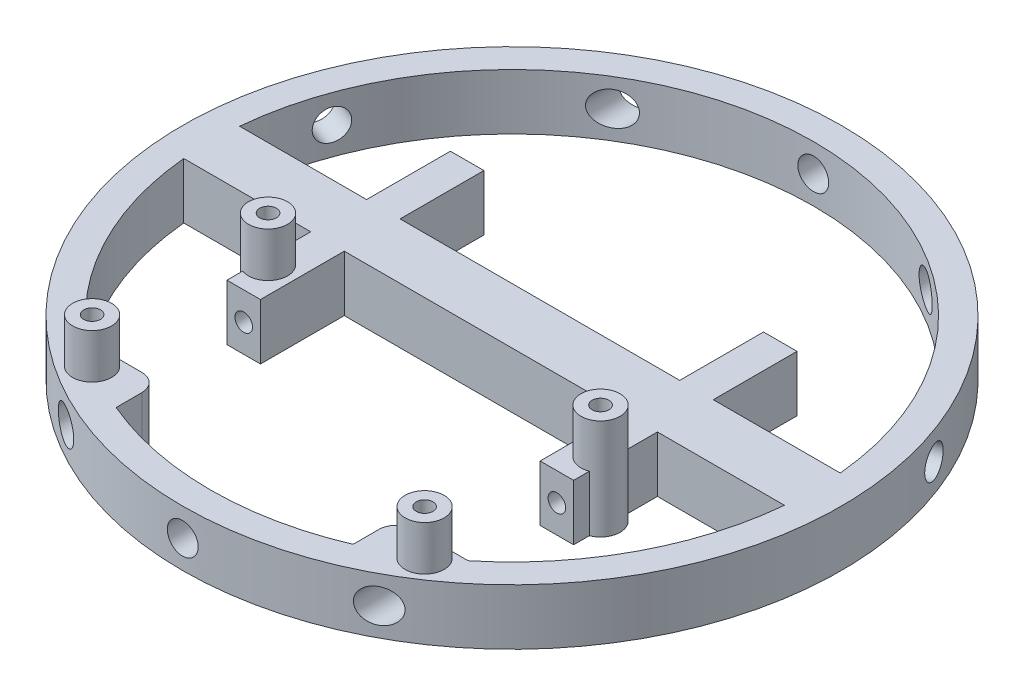
SolidWorks part; units mm, degrees
ref_plane "Front Plane" through (0, 0, 0) normal (0, 0, 1) x (1, 0, 0)
ref_plane "Top Plane" through (0, 0, 0) normal (0, 1, 0) x (1, 0, 0)
ref_plane "Right Plane" through (0, 0, 0) normal (1, 0, 0) x (0, 0, -1)
sketch "Sketch1" plane through (0, 0, 0) normal (0, 1, 0) x (1, 0, 0)
  line L5 (-50.7584, -5.9362) -> (-84.9011, -5.9362)
  line L6 (-84.9011, -5.9362) -> (-16.6157, -5.9362)
  line L9 (-84.9011, -12.2862) -> (-16.6157, -12.2862)
  circle A0 centre (-50.7584, -9.1112) radius 37.465
  circle A3 centre (-50.7584, -9.1112) radius 34.29
extrude "Boss-Extrude1" add sketch "Sketch1" along normal blind 6.35
sketch "Sketch2" plane through (0, 0, 17.0862) normal (0, 0, 1) x (1, 0, 0)
  circle A4 centre (-32.9584, 3.175) radius 0.9
  circle A5 centre (-68.5584, 3.175) radius 1
extrude "Cut-Extrude1" cut sketch "Sketch2" against normal blind 23.35
sketch "Sketch4" plane through (0, 6.35, 0) normal (0, 1, 0) x (1, 0, 0)
  line L1 (-73.4626, -34.8079) -> (-28.0542, -34.8079)
  line L5 (-69.2578, -37.9829) -> (-32.259, -37.9829)
  arc A0 (-84.9419, -11.8112) -> (-16.5749, -11.8112) centre (-50.7584, -9.1112) ccw construction
sketch "Sketch5" plane through (0, 6.35, 0) normal (0, 1, 0) x (1, 0, 0)
  line L3 (-83.3956, -19.6287) -> (-18.1212, -19.6287)
  line L7 (-29.3708, -35.9137) -> (-72.146, -35.9137)
  line L11 (-84.386, -15.8187) -> (-17.1308, -15.8187)
  line L12 (-66.2076, -39.7237) -> (-35.3092, -39.7237)
  arc A1 (-84.9419, -11.8112) -> (-16.5749, -11.8112) centre (-50.7584, -9.1112) ccw construction
sketch "Sketch6" plane through (0, 6.35, 0) normal (0, 1, 0) x (1, 0, 0)
  circle A0 centre (-31.8584, -37.9459) radius 0.8
  circle A1 centre (-69.6584, -37.9459) radius 0.8
  circle A2 centre (-69.6584, -17.9459) radius 0.8
  circle A3 centre (-31.8584, -17.9459) radius 0.8
sketch "Sketch7" plane through (-50.7584, 282.655, 9.1112) normal (1, 0, -0.0007) x (0.0007, 0, 1)
  circle A1 centre (0, 279.4192) radius 1.6802
sketch "Sketch8" plane through (0, 0, 6.4112) normal (0, 0, -1) x (-1, 0, 0)
  line L0 (68.5584, 3.175) -> (68.5584, 6.35)
  line L1 (84.9419, 6.35) -> (16.5749, 6.35) construction
  line L2 (68.5584, 6.35) -> (65.3834, 6.35)
  circle A0 centre (68.5584, 3.175) radius 1.25
sketch "Sketch9" plane through (0, 0, 12.2862) normal (0, 0, 1) x (1, 0, 0)
  line L0 (-70.4634, 6.35) -> (-66.6534, 6.35)
  line L2 (-13.2934, 0) -> (-88.2234, 0) construction
  line L7 (-70.4634, 0) -> (-66.6534, 0)
  line L8 (-70.4634, 6.35) -> (-70.4634, 0)
  line L9 (-66.6534, 0) -> (-66.6534, 6.35)
  circle A0 centre (-68.5584, 3.175) radius 1.25
extrude "Boss-Extrude4" add sketch "Sketch9" along normal blind 9.525 and the other way blind 15.875
sketch "Sketch10" plane through (0, 0, 12.2862) normal (0, 0, 1) x (1, 0, 0)
  circle A1 centre (-68.5584, 3.175) radius 1.25
  circle A2 centre (-68.5584, 3.175) radius 1
extrude "Boss-Extrude5" add sketch "Sketch10" along normal up to surface and the other way up to surface up to face at (-67.3084, 3.175, 21.8112) other way up to face at (-67.3084, 3.175, -3.5888)
sketch "Sketch11" plane through (0, 0, 5.9362) normal (0, 0, -1) x (-1, 0, 0)
  line L0 (31.0534, 6.35) -> (34.8634, 6.35)
  line L2 (31.0534, 0) -> (34.8634, 0)
  line L8 (31.0534, 6.35) -> (31.0534, 0)
  line L10 (34.8634, 6.35) -> (34.8634, 0)
  circle A0 centre (32.9584, 3.175) radius 0.9
extrude "Boss-Extrude6" add sketch "Sketch11" along normal up to surface and the other way up to surface
sketch "Sketch12" plane through (0, 0, 21.8112) normal (0, 0, 1) x (1, 0, 0)
  circle A0 centre (-32.9584, 3.175) radius 1
extrude "Cut-Extrude4" cut sketch "Sketch12" against normal blind 14.508
sketch "Sketch13" plane through (0, 6.35, 0) normal (0, 1, 0) x (1, 0, 0)
  circle A9 centre (-69.6584, -17.9459) radius 0.95
  circle A10 centre (-69.6584, -17.9459) radius 2.2225
  circle A11 centre (-31.8584, -17.9459) radius 0.95
  circle A12 centre (-31.8584, -17.9459) radius 2.2225
  circle A13 centre (-69.6584, -37.9459) radius 2.2225
  circle A14 centre (-69.6584, -37.9459) radius 0.95
  circle A15 centre (-31.8584, -37.9459) radius 2.2225
  circle A16 centre (-31.8584, -37.9459) radius 0.95
extrude "Boss-Extrude7" add sketch "Sketch13" along normal blind 5.08
sketch "Sketch17" plane through (0, 0, 21.8112) normal (0, 0, 1) x (1, 0, 0)
  circle A1 centre (-68.5584, 3.175) radius 1.905
sketch "Sketch18" plane through (0, 0, 21.8112) normal (0, 0, 1) x (1, 0, 0)
  circle A0 centre (-32.9584, 3.175) radius 1.905
sketch "Sketch19" plane through (0, 0, -3.5888) normal (0, 0, -1) x (-1, 0, 0)
  circle A0 centre (32.9584, 3.175) radius 1.905
  circle A1 centre (68.5584, 3.175) radius 1.905
sketch "Sketch20" plane through (0, 6.35, 0) normal (0, 1, 0) x (1, 0, 0)
  line L0 (-84.977, -6.8992) -> (-16.5429, -6.8525)
  line L1 (-84.977, -6.8992) -> (-16.5429, -6.8525) construction
  line L2 (-84.9739, -11.37) -> (-16.5398, -11.3233)
  line L3 (-84.9739, -11.37) -> (-16.5398, -11.3233) construction
  line L4 (-70.4634, -5.9362) -> (-70.4627, -6.8893)
  line L5 (-66.6534, -5.9362) -> (-66.6527, -6.8867)
  line L6 (-70.4634, -12.2862) -> (-70.4639, -11.569)
  line L7 (-70.4634, -12.2862) -> (-70.464, -11.3601) construction
  line L8 (-70.4639, -11.569) -> (-70.464, -11.3601)
  line L9 (-66.6534, -12.2862) -> (-66.654, -11.3575)
  line L10 (-34.8634, -5.9362) -> (-34.8628, -6.865)
  line L11 (-31.0534, -5.9362) -> (-31.0528, -6.8624)
  line L12 (-34.864, -11.3358) -> (-34.8634, -12.2862)
  line L13 (-31.054, -11.3332) -> (-31.0534, -12.2862)
  circle A0 centre (-50.7584, -9.1112) radius 34.29
sketch "Sketch21" plane through (0, 0, 0) normal (0, -1, 0) x (1, 0, 0)
  line L0 (-50.7584, 9.1112) -> (-63.5722, -26.0944)
  line L1 (-50.7584, 9.1112) -> (-50.7584, -28.3538)
  circle A0 centre (-50.7584, 9.1112) radius 37.465 construction
  dimension "D1" = 20
ref_plane "Plane1" through (-63.5722, 0, -26.0944) normal (-0.342, 0, -0.9397) x (-0.9397, 0, 0.342)
sketch "Sketch22" plane through (-63.5722, 0, -26.0944) normal (-0.342, 0, -0.9397) x (-0.9397, 0, 0.342)
  circle A0 centre (0, 3.175) radius 1.7526
sketch "Sketch23" plane through (0, 6.35, 0) normal (0, -1, 0) x (1, 0, 0)
  circle A1 centre (-69.6584, 37.9459) radius 2.2225
  circle A2 centre (-31.8584, 37.9459) radius 2.2225
  circle A3 centre (-31.8584, 17.9459) radius 2.2225
  circle A4 centre (-69.6584, 17.9459) radius 2.2225
extrude "Cut-Extrude6" cut sketch "Sketch19" along normal blind 31
sketch "Sketch25" plane through (0, 0, 21.8112) normal (0, 0, 1) x (1, 0, 0)
  circle A0 centre (-32.9584, 3.175) radius 1.905
  circle A1 centre (-68.5584, 3.175) radius 1.905
extrude "Cut-Extrude8" cut sketch "Sketch25" along normal blind 50
sketch "Sketch27" plane through (0, 6.35, 0) normal (0, 1, 0) x (1, 0, 0)
  line L0 (-69.6584, -35.7234) -> (-72.3824, -35.7234)
  line L1 (-72.3824, -35.7234) -> (-66.2292, -35.7234)
  line L2 (-64.2292, -37.7234) -> (-64.2292, -40.6444)
  line L3 (-50.7584, -12.2862) -> (-50.7584, -36.3026)
  line L4 (-66.6534, -12.2862) -> (-34.8634, -12.2862) construction
  line L5 (-29.1344, -35.7234) -> (-35.2875, -35.7234)
  line L6 (-37.2875, -37.7234) -> (-37.2875, -40.6444)
  circle A0 centre (-69.6584, -37.9459) radius 2.2225 construction
  arc A1 (-84.9011, -12.2862) -> (-71.3632, -36.52) centre (-50.7584, -9.1112) ccw construction
  arc A2 (-67.6708, -38.9403) -> (-33.846, -38.9403) centre (-50.7584, -9.1112) ccw construction
  arc A3 (-64.2292, -37.7234) -> (-66.2292, -35.7234) centre (-66.2292, -37.7234) ccw
  arc A4 (-37.2875, -37.7234) -> (-35.2875, -35.7234) centre (-35.2875, -37.7234) cw
  circle A5 centre (-50.7584, -9.1112) radius 34.29
  arc M4 (-16.6157, -12.2862) -> (-30.1535, -36.52) centre (-50.7584, -9.1112) cw
  arc M6 (-33.846, -38.9403) -> (-67.6708, -38.9403) centre (-50.7584, -9.1112) cw
  arc M8 (-71.3632, -36.52) -> (-84.9011, -12.2862) centre (-50.7584, -9.1112) cw
  dimension "D1" = 2
extrude "Boss-Extrude12" add sketch "Sketch27" against normal up to surface (6.35 mm away) contours A5 L2 A3 L1 L0 M8 M6 | A5 L5 A4 L6 M6 M4 up to face at (-50.7584, 0, 19.2077)
sketch "Sketch24" plane through (0, 0, 21.8112) normal (0, 0, 1) x (1, 0, 0)
  circle A0 centre (-68.5584, 3.175) radius 1.905
  circle A1 centre (-32.9584, 3.175) radius 1.905
extrude "Cut-Extrude5" cut sketch "Sketch24" along normal blind 31
sketch "Sketch28" plane through (0, 6.35, 0) normal (0, -1, 0) x (1, 0, 0)
  line L0 (-70.4564, 15.8716) -> (-70.4634, 20.0175)
  line L1 (-50.7584, 12.2862) -> (-50.7584, 6.5712)
  line L2 (-66.6534, 12.2862) -> (-34.8634, 12.2862) construction
  line L3 (-31.0604, 15.8716) -> (-31.0534, 20.0175)
  circle A0 centre (-69.6584, 17.9459) radius 2.2225
  circle A1 centre (-31.8584, 17.9459) radius 2.2225
  arc M1 (-70.4634, 20.0175) -> (-70.4634, 15.8743) centre (-69.6584, 17.9459) ccw
  line M2 (-70.4634, 15.8743) -> (-70.4634, 17.4415)
  arc M3 (-70.4634, 17.4415) -> (-70.4634, 18.4503) centre (-69.6584, 17.9459) cw
  line M4 (-70.4634, 18.4503) -> (-70.4634, 20.0175)
extrude "Boss-Extrude13" add sketch "Sketch28" along normal up to surface (6.35 mm away) contours M4 M1 M2 M3 | A0 L0 M2 M4 M3 | A1 L3
sketch "Sketch30" plane through (0, 0, 0) normal (0, 0, 1) x (1, 0, 0)
  circle A0 centre (-50.7584, 3.175) radius 1.7526
extrude "Cut-Extrude9" cut sketch "Sketch30" against normal blind 5 from offset 24 offset against normal yes
pattern_circular "CirPattern2" count 2 every 70 of "Cut-Extrude9"
sketch "Sketch31" plane through (0, 0, 12.2862) normal (0, 0, 1) x (1, 0, 0)
  circle A0 centre (-50.7584, 3.175) radius 1.7526
extrude "Cut-Extrude10" cut sketch "Sketch31" along normal blind 60
